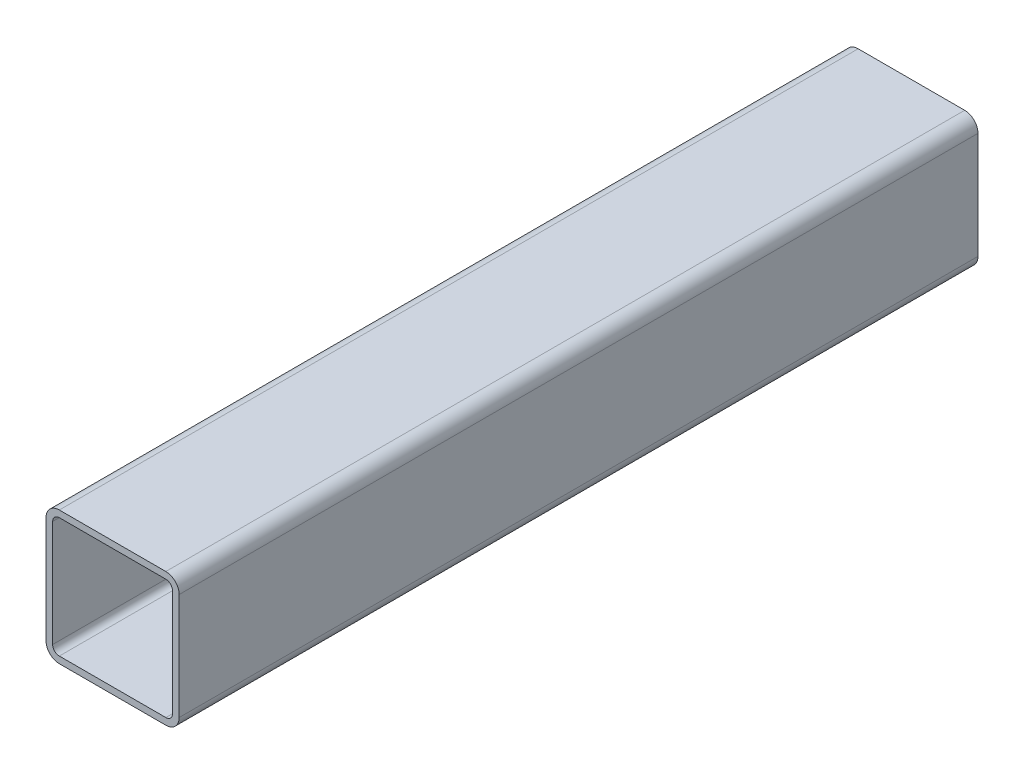
SolidWorks part; units mm, degrees
ref_plane "Front Plane" through (0, 0, 0) normal (0, 0, 1) x (1, 0, 0)
ref_plane "Top Plane" through (0, 0, 0) normal (0, 1, 0) x (1, 0, 0)
ref_plane "Right Plane" through (0, 0, 0) normal (1, 0, 0) x (0, 0, -1)
sketch "Sketch1" plane through (0, 0, 0) normal (0, 0, 1) x (1, 0, 0)
  line L0 (-40, 45) -> (40, 45)
  line L1 (-40, -50) -> (40, -50)
  line L2 (-50, -40) -> (-50, 40)
  line L3 (-40, 50) -> (40, 50)
  line L4 (50, -40) -> (50, 40)
  line L5 (-50, -50) -> (50, 50) construction
  line L6 (-50, 50) -> (50, -50) construction
  line L7 (45, -40) -> (45, 40)
  line L8 (-40, -45) -> (40, -45)
  line L9 (-45, -40) -> (-45, 40)
  arc A0 (-40, 50) -> (-50, 40) centre (-40, 40) ccw
  arc A1 (-50, -40) -> (-40, -50) centre (-40, -40) ccw
  arc A2 (40, -50) -> (50, -40) centre (40, -40) ccw
  arc A3 (50, 40) -> (40, 50) centre (40, 40) ccw
  arc A4 (45, 40) -> (40, 45) centre (40, 40) ccw
  arc A5 (40, -45) -> (45, -40) centre (40, -40) ccw
  arc A6 (-45, -40) -> (-40, -45) centre (-40, -40) ccw
  arc A7 (-40, 45) -> (-45, 40) centre (-40, 40) ccw
  point P0 (0, 0)
  dimension "D2" = 10
  dimension "D1" = 100
  dimension "D3" = 5
extrude "Boss-Extrude1" add sketch "Sketch1" along normal blind 600
